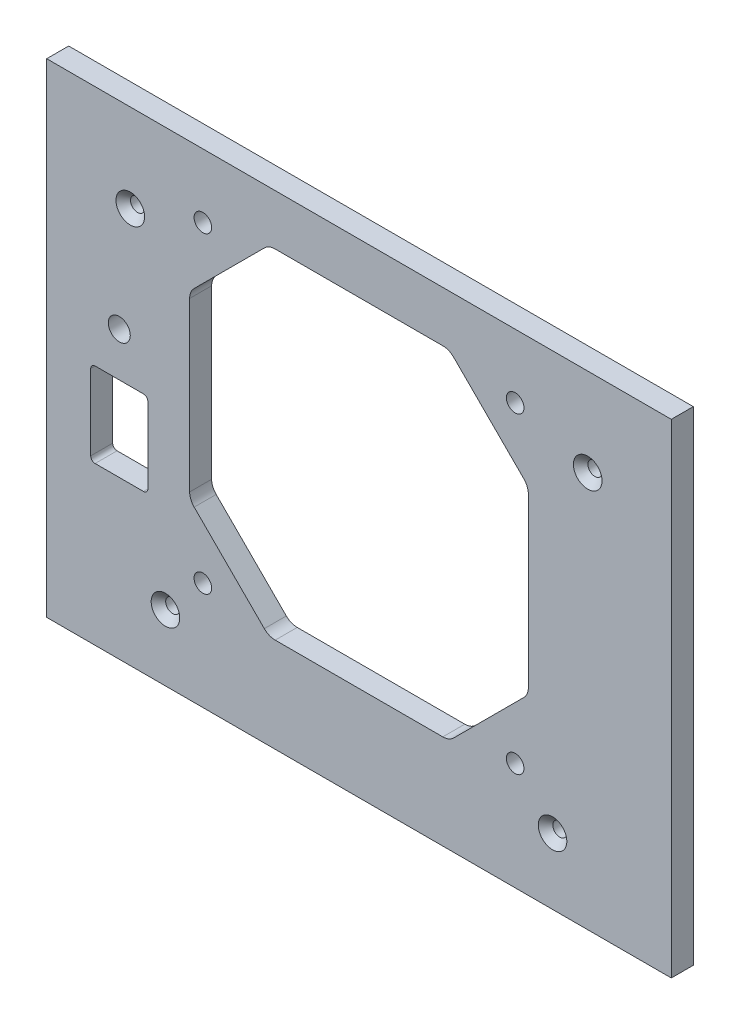
SolidWorks part; units mm, degrees
material "Polycarbonate (PC)"
ref_plane "Front Plane" through (0, 0, 0) normal (0, 0, 1) x (1, 0, 0)
ref_plane "Top Plane" through (0, 0, 0) normal (0, 1, 0) x (1, 0, 0)
ref_plane "Right Plane" through (0, 0, 0) normal (1, 0, 0) x (0, 0, -1)
sketch "Sketch1" plane through (0, 0, 0) normal (0, 0, 1) x (1, 0, 0)
  line L1 (71, -55) -> (-71, -55)
  line L2 (71, -55) -> (71, 55)
  line L3 (71, 55) -> (-71, 55)
  line L4 (-71, -55) -> (-71, 55)
  line L5 (71, -55) -> (-71, 55) construction
  line L6 (71, 55) -> (-71, -55) construction
  point P0 (0, 0)
  dimension "D1" = 142
  dimension "D2" = 110
extrude "Sheet" add sketch "Sketch1" along normal mid plane 5
sketch "Sketch7" plane through (0, 0, 2.5) normal (0, 0, 1) x (1, 0, 0)
  line L0 (-20.5, 43.5) -> (-38.5, 25.5)
  line L1 (20.5, -33.5) -> (-20.5, -33.5)
  line L2 (38.5, -15.5) -> (38.5, 25.5)
  line L3 (20.5, 43.5) -> (-20.5, 43.5)
  line L4 (-38.5, -15.5) -> (-38.5, 25.5)
  line L5 (38.5, -33.5) -> (-38.5, 43.5) construction
  line L6 (38.5, 43.5) -> (-38.5, -33.5) construction
  line L7 (-20.5, -33.5) -> (-38.5, -15.5)
  line L8 (38.5, -15.5) -> (20.5, -33.5)
  line L9 (38.5, 25.5) -> (20.5, 43.5)
  circle A0 centre (0, 5) radius 38.5 construction
  circle A1 centre (-35.5, -30.5) radius 2
  circle A2 centre (35.5, -30.5) radius 2
  circle A3 centre (35.5, 40.5) radius 2
  circle A4 centre (-35.5, 40.5) radius 2
  dimension "D3" = 4
  dimension "D10" = 77
  dimension "D2" = 5
  dimension "D4" = 71
  dimension "D5" = 71
  dimension "D11" = 77
extrude "FanHoles" cut sketch "Sketch7" against normal through all
chamfer "FanChamfer" [suppressed] distance 3 angle 45
fillet "Fillet1" radius 3.5 8 edges at (38.5, 25.5, 0) (38.5, -15.5, 0) (20.5, -33.5, 0) (-38.5, -15.5, 0) (-38.5, 25.5, 0) (-20.5, 43.5, 0) (20.5, 43.5, 0) (-20.5, -33.5, 0)
hole_wizard "Ø3.2 (3.2) TopMountHoles" positions "Sketch9" profile "Sketch10" hole size "Ø3.2" standard "ANSI Metric" end condition through all
sketch "Sketch9" plane through (0, 0, 2.5) normal (0, 0, 1) x (1, 0, 0)
  line L0 (71, 55) -> (-71, 55) construction
  line L1 (-71, 55) -> (-71, -55) construction
  line L2 (71, -55) -> (71, 55) construction
  point P0 (-52, 35)
  point P2 (52, 35)
  dimension "D1" = 20
  dimension "D2" = 19
  dimension "D3" = 19
sketch "Sketch10" plane through (-52, 35, 2.5) normal (1, 0, 0) x (0, -1, 0)
  line L0 (0, 0) -> (0, 5)
  line L1 (0, 5) -> (1.6, 5)
  line L2 (1.6, 5) -> (1.6, 1.65)
  line L3 (1.6, 1.65) -> (3.25, 0)
  line L5 (3.25, 0) -> (0, 0)
  line L6 (-1.6, 1.65) -> (-3.25, 0) construction
  line L11 (0, -6.35) -> (0, 107.95) construction
  dimension "Thru Hole Dia." = 3.2
  dimension "Thru Hole Depth" = 5
  dimension "Near C'Sink Dia." = 6.5
  dimension "Near C'Sink Angle" = 90
hole_wizard "Ø3.2 (3.2) BottomMountHoles" positions "Sketch11" profile "Sketch12" hole size "Ø3.2" standard "ANSI Metric" end condition through all
sketch "Sketch11" plane through (0, 0, 2.5) normal (0, 0, 1) x (1, 0, 0)
  line L0 (-71, -55) -> (71, -55) construction
  line L1 (-71, 55) -> (-71, -55) construction
  line L2 (71, -55) -> (71, 55) construction
  point P0 (-44, -40)
  point P2 (44, -40)
  dimension "D1" = 15
  dimension "D2" = 27
  dimension "D3" = 27
sketch "Sketch12" plane through (-44, -40, 2.5) normal (1, 0, 0) x (0, -1, 0)
  line L0 (0, 0) -> (0, 5)
  line L1 (0, 5) -> (1.6, 5)
  line L2 (1.6, 5) -> (1.6, 1.65)
  line L3 (1.6, 1.65) -> (3.25, 0)
  line L5 (3.25, 0) -> (0, 0)
  line L6 (-1.6, 1.65) -> (-3.25, 0) construction
  line L11 (0, -6.35) -> (0, 107.95) construction
  dimension "Thru Hole Dia." = 3.2
  dimension "Thru Hole Depth" = 5
  dimension "Near C'Sink Dia." = 6.5
  dimension "Near C'Sink Angle" = 90
sketch "Sketch13" plane through (0, 0, 2.5) normal (0, 0, 1) x (1, 0, 0)
  line L0 (-71, 55) -> (-71, -55) construction
  line L1 (-60, 0) -> (-49, 0)
  line L2 (-61, -1) -> (-61, -18.2)
  line L3 (-60, -19.2) -> (-49, -19.2)
  line L4 (-48, -1) -> (-48, -18.2)
  line L5 (71, 55) -> (-71, 55) construction
  arc A0 (-49, -19.2) -> (-48, -18.2) centre (-49, -18.2) ccw
  arc A1 (-61, -18.2) -> (-60, -19.2) centre (-60, -18.2) ccw
  arc A2 (-49, 0) -> (-48, -1) centre (-49, -1) cw
  arc A3 (-60, 0) -> (-61, -1) centre (-60, -1) ccw
  point P8 (-61, -19.2)
  point P11 (-48, 0)
  point P14 (-61, 0)
  dimension "D3" = 1
  dimension "D1" = 13
  dimension "D2" = 19.2
  dimension "D4" = 10
  dimension "D5" = 55
extrude "SwitchSlot" cut sketch "Sketch13" against normal through all
sketch "Sketch8" plane through (0, 0, 2.5) normal (0, 0, 1) x (1, 0, 0)
  line L0 (-49, 0) -> (-60, 0) construction
  circle A0 centre (-54.5, 10) radius 2.5
  point P7 (-54.5, 0)
  dimension "D1" = 10
  dimension "D2" = 5
extrude "LEDHole" cut sketch "Sketch8" against normal through all
equation "\"D3@Sketch9\"=\"D2@Sketch9\""
equation "\"D3@Sketch11\"=\"D2@Sketch11\""
